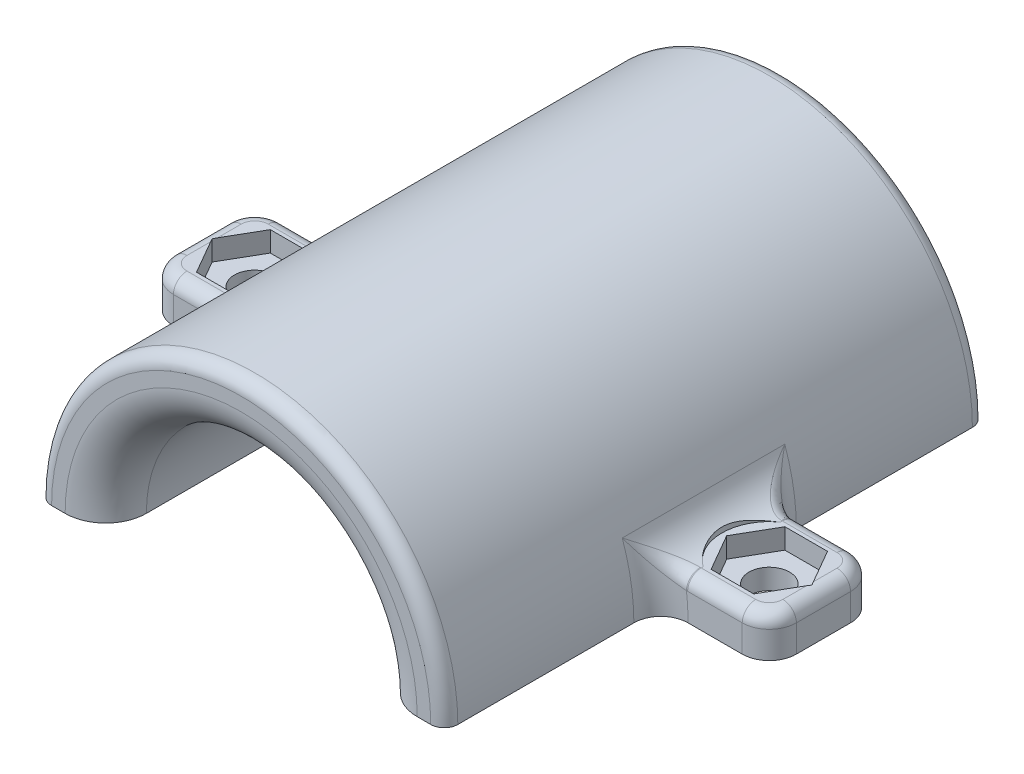
SolidWorks part; units mm, degrees
material "ABS"
ref_plane "Front Plane" through (0, 0, 0) normal (0, 0, 1) x (1, 0, 0)
ref_plane "Top Plane" through (0, 0, 0) normal (0, 1, 0) x (1, 0, 0)
ref_plane "Right Plane" through (0, 0, 0) normal (1, 0, 0) x (0, 0, -1)
sketch "Sketch1" plane through (0, 0, 0) normal (0, 0, 1) x (1, 0, 0)
  line L0 (-10, 0) -> (10, 0)
  line L1 (-15, 0) -> (15, 0)
  arc A0 (-10, 0) -> (10, 0) centre (0, 0) cw
  arc A1 (-15, 0) -> (15, 0) centre (0, 0) cw
  point P4 (0, 0)
  point P9 (0, 0)
  dimension "D2" = 5
  dimension "D1" = 20
extrude "Boss-Extrude1" add sketch "Sketch1" along normal blind 40 contours A1 L1 A0 region at (-12.5, 0.3354, 0)
sketch "Sketch2" plane through (0, 0, 0) normal (0, -1, 0) x (1, 0, 0)
  line L0 (-15, 40) -> (-15, 0) construction
  line L1 (-10, 24) -> (-23, 24)
  line L2 (-10, 24) -> (-10, 16)
  line L3 (-10, 16) -> (-23, 16)
  line L4 (-23, 24) -> (-23, 16)
  line L5 (15, 0) -> (15, 40) construction
  line L6 (-10, 40) -> (-10, 0) construction
  circle A0 centre (-19, 20) radius 1.5
  point P10 (-23, 20)
  point P14 (15, 20)
  point P15 (-10, 20)
  dimension "D1" = 3
  dimension "D2" = 4
  dimension "D3" = 4
  dimension "D4" = 4
extrude "Boss-Extrude2" add sketch "Sketch2" against normal blind 3
mirror "Mirror1" about plane through (0, 0, 0) normal (1, 0, 0) of "Boss-Extrude2"
fillet "Fillet1" radius 3 4 edges at (0, 10, 0) (14.6969, 3, 20) (-14.6969, 3, 20) (0, 10, 40)
fillet "Fillet2" radius 2 4 edges at (-23, 1.5, 24) (-23, 1.5, 16) (23, 1.5, 16) (23, 1.5, 24)
fillet "Fillet3" radius 2 4 edges at (-14.784, 2.5365, 16) (14.784, 2.5365, 16) (14.784, 2.5365, 24) (-14.784, 2.5365, 24)
fillet "Fillet4" radius 1 20 edges at (-15.3779, 3.4577, 15.5706) (-16.8509, 3.0024, 16) (-18.9853, 3, 16) (-22.4142, 3, 16.5858) (-23, 3, 20) (-22.4142, 3, 23.4142) (-18.9853, 3, 24) (15.3779, 3.4577, 15.5706) (16.8509, 3.0024, 16) (18.9853, 3, 16) (22.4142, 3, 16.5858) (23, 3, 20) (22.4142, 3, 23.4142) (18.9853, 3, 24) (0, 15, 0) (0, 15, 40) (15.3779, 3.4577, 24.4294) (16.8509, 3.0024, 24) (-15.3779, 3.4577, 24.4294) (-16.8509, 3.0024, 24)
sketch "Sketch3" plane through (0, 3, 0) normal (0, 1, 0) x (1, 0, 0)
  circle A0 centre (-19, -20) radius 3.5
  dimension "D1" = 7
extrude "Cut-Extrude1" cut sketch "Sketch3" along normal through all
mirror "Mirror3" about plane through (0, 0, 0) normal (1, 0, 0) of "Cut-Extrude1"
sketch "Sketch4" plane through (0, 3, 0) normal (0, 1, 0) x (1, 0, 0)
  line L0 (-16.9706, -24) -> (-21, -24) construction
  line L1 (-20.5733, -22.725) -> (-17.4267, -22.725)
  line L2 (-17.4267, -22.725) -> (-15.8534, -20)
  line L3 (-15.8534, -20) -> (-17.4267, -17.275)
  line L4 (-17.4267, -17.275) -> (-20.5733, -17.275)
  line L5 (-20.5733, -17.275) -> (-22.1466, -20)
  line L6 (-22.1466, -20) -> (-20.5733, -22.725)
  line L7 (0, 0) -> (0, -40) construction
  line L8 (-14, -40) -> (14, -40) construction
  line L9 (22.1466, -20) -> (20.5733, -22.725)
  line L10 (20.5733, -17.275) -> (22.1466, -20)
  line L11 (17.4267, -17.275) -> (20.5733, -17.275)
  line L12 (15.8534, -20) -> (17.4267, -17.275)
  line L13 (17.4267, -22.725) -> (15.8534, -20)
  line L14 (20.5733, -22.725) -> (17.4267, -22.725)
  circle A0 centre (-19, -20) radius 2.725 construction
  circle A1 centre (19, -20) radius 2.725 construction
  dimension "D1" = 5.45
extrude "Cut-Extrude2" cut sketch "Sketch4" against normal blind 1.5
